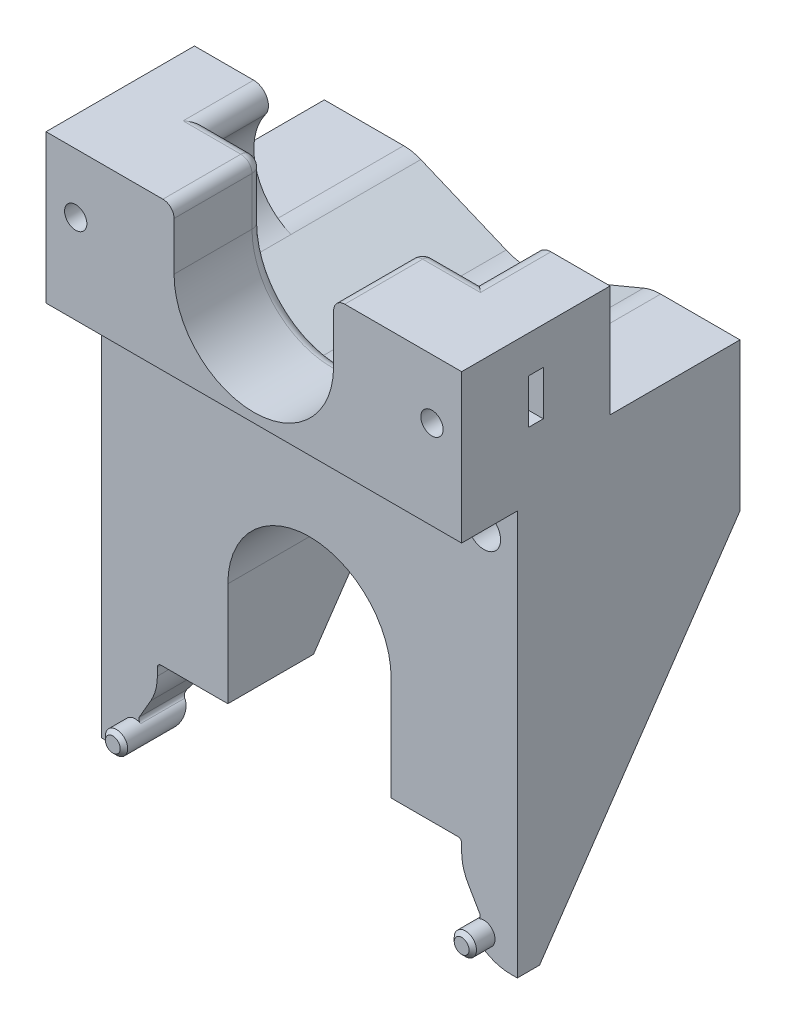
SolidWorks part; units mm, degrees
ref_plane "Front Plane" through (0, 0, 0) normal (0, 0, 1) x (1, 0, 0)
ref_plane "Top Plane" through (0, 0, 0) normal (0, 1, 0) x (1, 0, 0)
ref_plane "Right Plane" through (0, 0, 0) normal (1, 0, 0) x (0, 0, -1)
sketch "Sketch2" plane through (0, 0, 0) normal (0, 0, 1) x (1, 0, 0)
  line L0 (0, 28) -> (0, 0) construction
  line L1 (-23.5, -23.5) -> (23.5, -23.5) construction
  line L2 (-23.5, -23.5) -> (-23.5, 23.5) construction
  line L3 (-23.5, 23.5) -> (23.5, 23.5) construction
  line L4 (23.5, -23.5) -> (23.5, 23.5) construction
  line L5 (-23.5, -23.5) -> (23.5, 23.5) construction
  line L6 (-23.5, 23.5) -> (23.5, -23.5) construction
  line L7 (-28, -37) -> (28, -37) construction
  line L8 (-28, -37) -> (-28, 28) construction
  line L9 (-28, 28) -> (28, 28) construction
  line L10 (28, -37) -> (28, 28) construction
  line L11 (0, 0) -> (-28, 0) construction
  line L12 (-23.5, -25.5) -> (-23.5, -26.5) construction
  line L13 (-23.5, -26.5) -> (23.5, -26.5) construction
  line L14 (23.5, -26.5) -> (23.5, -25.5) construction
  line L15 (-23.5, -25.5) -> (23.5, -25.5) construction
  line L16 (0, 28) -> (0, 29.5) construction
  line L17 (0, 29.5) -> (0, 40) construction
  circle A0 centre (23.5, 23.5) radius 2 construction
  circle A1 centre (-23.5, 23.5) radius 2.25
  circle A2 centre (-23.5, -23.5) radius 1.5
  circle A3 centre (23.5, -23.5) radius 2 construction
  circle A4 centre (23.5, 23.5) radius 2.25
  circle A5 centre (23.5, -23.5) radius 1.5
  circle A6 centre (0, 40) radius 10.5 construction
  point P0 (0, 0)
  dimension "D3" = 4
  dimension "D8" = 21
  dimension "D1" = 47
  dimension "D5" = 56
  dimension "D6" = 65
  dimension "D7" = 1
  dimension "D9" = 1.5
  dimension "D4" = 0.5
sketch "Sketch3" plane through (0, 0, 0) normal (1, 0, 0) x (0, 0, -1)
  line L0 (0, -26.5) -> (0, 0)
  line L1 (0, 0) -> (0, 28)
  line L3 (30, 48) -> (30, 13)
  line L4 (30, 13) -> (3, -26.5)
  line L5 (3, -26.5) -> (0, -26.5)
  line L6 (30, 48) -> (-7.5, 48)
  line L7 (-7.5, 48) -> (-7.5, 28)
  line L8 (-7.5, 28) -> (0, 28)
  line L9 (0, 28) -> (30, 28) construction
  line L10 (3, -26.5) -> (22.1727, -26.5) construction
  dimension "D1" = 15
  dimension "D2" = 20
  dimension "D3" = 30
  dimension "D4" = 3
  dimension "D5" = 55.646
  dimension "D6" = 7.5
extrude "Boss-Extrude1" add sketch "Sketch3" along normal up to vertex (28 mm away) and the other way up to vertex (28 mm away) up to point (28, 28, 0) other way up to point (-28, 28, 0)
sketch "Sketch4" plane through (0, 0, 0) normal (0, 0, 1) x (1, 0, 0)
  line L0 (-28, -26.5) -> (-27.1213, -26.5) construction
  line L1 (-23.5, -26.5) -> (23.5, -26.5) construction
  line L2 (28, -26.5) -> (-28, -26.5) construction
  line L3 (-22.933, -21.5179) -> (-21.3871, -18.8403)
  line L4 (-27.1213, -26.5) -> (27.1213, -26.5)
  line L5 (0, 28) -> (0, -26.5) construction
  line L6 (-23.5, -23.5) -> (-23.5, 23.5) construction
  line L7 (-23.5, -23.5) -> (-22.75, -22.201) construction
  line L8 (-23.5, -23.5) -> (-22.4393, -24.5607) construction
  line L9 (-23.5, -23.5) -> (23.5, 23.5) construction
  line L10 (-22, -23.5) -> (-20.5, -23.5) construction
  line L11 (-23.5, -23.5) -> (23.5, -23.5) construction
  line L12 (-20.5, -15.5297) -> (-20.5, -14.5)
  line L13 (-20.5, -15.5297) -> (-20.5, -23.5) construction
  line L14 (-28, 28) -> (28, 28) construction
  line L15 (-20, -14) -> (-11, -14)
  line L16 (0, 0) -> (-28, 0) construction
  line L17 (-11, 0) -> (-11, -14)
  line L19 (28, -26.5) -> (27.1213, -26.5) construction
  line L20 (11, 0) -> (11, -14)
  line L21 (20, -14) -> (11, -14)
  line L22 (20.5, -15.5297) -> (20.5, -14.5)
  line L23 (22.933, -21.5179) -> (21.3871, -18.8403)
  arc A0 (-22.4393, -24.5607) -> (-22.75, -22.201) centre (-23.5, -23.5) ccw
  circle A1 centre (-23.5, -23.5) radius 1.5 construction
  arc A2 (-22.4393, -24.5607) -> (-27.1213, -26.5) centre (-27.1213, -19.8787) cw
  arc A3 (-22.75, -22.201) -> (-22.933, -21.5179) centre (-22.5, -21.7679) cw
  arc A4 (-21.3871, -18.8403) -> (-20.5, -15.5297) centre (-27.1213, -15.5297) ccw
  arc A5 (-11, 0) -> (11, 0) centre (0, 0) cw
  arc A6 (-20.5, -14.5) -> (-20, -14) centre (-20, -14.5) cw
  arc A7 (20.5, -14.5) -> (20, -14) centre (20, -14.5) ccw
  arc A8 (21.3871, -18.8403) -> (20.5, -15.5297) centre (27.1213, -15.5297) cw
  arc A9 (22.75, -22.201) -> (22.933, -21.5179) centre (22.5, -21.7679) ccw
  arc A10 (22.4393, -24.5607) -> (27.1213, -26.5) centre (27.1213, -19.8787) ccw
  arc A11 (22.4393, -24.5607) -> (22.75, -22.201) centre (23.5, -23.5) cw
  dimension "D1" = 0.5
  dimension "D5" = 22
  dimension "D2" = 30
  dimension "D3" = 1.5
  dimension "D4" = 42
extrude "Cut-Extrude1" cut sketch "Sketch4" against normal up to next
sketch "Sketch5" plane through (0, 0, 0) normal (0, 0, 1) x (1, 0, 0)
  circle A0 centre (23.5, -23.5) radius 1.5 construction
  circle A1 centre (-23.5, -23.5) radius 1.5 construction
  circle A2 centre (23.5, -23.5) radius 1.5
  circle A3 centre (-23.5, -23.5) radius 1.5
extrude "Boss-Extrude2" add sketch "Sketch5" along normal blind 3
chamfer "Chamfer1" distance 0.5 angle 45 2 edges at (25, -23.5, 3) (-22, -23.5, 3)
sketch "Sketch6" plane through (0, 0, 0) normal (0, 0, 1) x (1, 0, 0)
  circle A0 centre (23.5, 23.5) radius 2.25 construction
  circle A1 centre (-23.5, 23.5) radius 2.25 construction
  circle A2 centre (23.5, 23.5) radius 2.25
  circle A3 centre (-23.5, 23.5) radius 2.25
extrude "Cut-Extrude2" cut sketch "Sketch6" against normal up to next
sketch "Sketch7" plane through (0, 0, -30) normal (0, 0, -1) x (-1, 0, 0)
  circle A0 centre (-23.5, 23.5) radius 3.75
  circle A1 centre (23.5, 23.5) radius 3.5 construction
  circle A2 centre (23.5, 23.5) radius 3.75
  dimension "D2" = 7
  dimension "D1" = 0.25
extrude "Cut-Extrude3" cut sketch "Sketch7" against normal blind 3
sketch "Sketch8" plane through (0, 0, -30) normal (0, 0, -1) x (-1, 0, 0)
  line L4 (-10.5, 40) -> (10.5, 40) construction
  line L5 (-10.75, 40) -> (-10.75, 48)
  line L6 (-28, 48) -> (28, 48) construction
  line L7 (-10.75, 48) -> (10.75, 48)
  line L8 (10.75, 48) -> (10.75, 40)
  arc A0 (-10.5, 40) -> (10.5, 40) centre (0, 40) ccw construction
  circle A1 centre (0, 40) radius 10.5 construction
  arc A2 (-10.75, 40) -> (10.75, 40) centre (0, 40) ccw
  dimension "D1" = 0.25
extrude "Cut-Extrude4" cut sketch "Sketch8" against normal up to next
sketch "Sketch9" plane through (0, 0, -30) normal (0, 0, -1) x (-1, 0, 0)
  line L1 (3.5, 27.7009) -> (15.0026, 32.5)
  line L2 (0, 40) -> (20, 40) construction
  line L3 (0, 40) -> (0, 27) construction
  line L4 (10.75, 48) -> (28, 48) construction
  line L5 (20.0311, 48) -> (-20.0311, 48)
  line L6 (0, 48) -> (0, 40) construction
  line L7 (-3.5, 27.7009) -> (-15.0026, 32.5)
  arc A0 (-3.5, 27.7009) -> (3.5, 27.7009) centre (0, 36.0897) ccw
  arc A1 (18.42, 44.815) -> (15.0026, 32.5) centre (11.8734, 40) cw
  arc A2 (18.42, 44.815) -> (20.0311, 48) centre (20.0311, 46) cw
  arc A3 (-18.42, 44.815) -> (-15.0026, 32.5) centre (-11.8734, 40) ccw
  arc A4 (-18.42, 44.815) -> (-20.0311, 48) centre (-20.0311, 46) ccw
  dimension "D1" = 20
  dimension "D2" = 7.5
  dimension "D5" = 2
  dimension "D3" = 13
  dimension "D4" = 3.5
extrude "Cut-Extrude5" cut sketch "Sketch9" against normal offset from surface (25.5 mm away) 12 up to face at (0, 39.6563, 7.5)
fillet "Fillet1" radius 1.5 7 edges at (-10.75, 44, -4.5) (0, 29.25, -4.5) (-15.3905, 48, -4.5) (-10.75, 48, 1.5) (10.75, 44, -4.5) (10.75, 48, 1.5) (15.3905, 48, -4.5)
sketch "Sketch10" plane through (0, 0, -30) normal (0, 0, -1) x (-1, 0, 0)
  line L0 (3.5, 27.7009) -> (15.0026, 32.5) construction
  line L1 (17.3129, 32.9626) -> (28, 32.9626)
  line L2 (28, 13) -> (28, 48) construction
  line L3 (20.0311, 48) -> (28, 48) construction
  line L4 (20.0311, 48) -> (28, 48)
  line L5 (28, 32.9626) -> (28, 48)
  line L6 (0, 52.0975) -> (0, 21.7333) construction
  line L7 (-17.3129, 32.9626) -> (-28, 32.9626)
  line L8 (-20.0311, 48) -> (-28, 48)
  line L9 (-28, 32.9626) -> (-28, 48)
  arc A0 (17.3129, 32.9626) -> (15.0026, 32.5) centre (17.3129, 26.9626) ccw
  arc A1 (20.0311, 48) -> (18.42, 44.815) centre (20.0311, 46) ccw construction
  arc A2 (15.0026, 32.5) -> (18.42, 44.815) centre (11.8734, 40) ccw construction
  arc A3 (20.0311, 48) -> (18.42, 44.815) centre (20.0311, 46) ccw
  arc A4 (15.0026, 32.5) -> (18.42, 44.815) centre (11.8734, 40) ccw
  arc A5 (-17.3129, 32.9626) -> (-15.0026, 32.5) centre (-17.3129, 26.9626) cw
  arc A6 (-15.0026, 32.5) -> (-18.42, 44.815) centre (-11.8734, 40) cw
  arc A7 (-20.0311, 48) -> (-18.42, 44.815) centre (-20.0311, 46) cw
  dimension "D1" = 6
extrude "Cut-Extrude6" cut sketch "Sketch10" against normal offset from surface (17.5 mm away) 8 up to face at (0, 38.4455, -4.5)
sketch "Sketch11" plane through (0, 0, -12.5) normal (0, 0, -1) x (-1, 0, 0)
  line L0 (20, 40) -> (28, 40) construction
  line L1 (28, 48) -> (28, 32.9626) construction
  line L2 (20, 40) -> (0, 40) construction
  line L3 (0, 35.0058) -> (0, 45.4651) construction
  circle A0 centre (24, 40) radius 1.25 construction
  arc A2 (15.0026, 32.5) -> (18.42, 44.815) centre (11.8734, 40) ccw construction
  circle A3 centre (24, 40) radius 1.5
  circle A4 centre (-24, 40) radius 1.5
  point P10 (24, 40)
  dimension "D1" = 0.25
  dimension "D2" = 2.5
extrude "Cut-Extrude7" cut sketch "Sketch11" against normal up to next
ref_plane "Plane1" through (0, 0, -2.5) normal (0, 0, -1) x (-1, 0, 0)
sketch "Sketch12" plane through (0, 0, -2.5) normal (0, 0, -1) x (-1, 0, 0)
  line L0 (21, 37) -> (28, 37)
  line L1 (21.25, 37.25) -> (26.75, 37.25) construction
  line L2 (21.25, 37.25) -> (21.25, 42.75) construction
  line L3 (21.25, 42.75) -> (26.75, 42.75) construction
  line L4 (26.75, 37.25) -> (26.75, 42.75) construction
  line L5 (21.25, 37.25) -> (26.75, 42.75) construction
  line L6 (21.25, 42.75) -> (26.75, 37.25) construction
  line L7 (21, 37) -> (21, 43)
  line L8 (21, 43) -> (28, 43)
  line L9 (21, 37) -> (26.75, 37) construction
  line L10 (21, 43) -> (26.75, 43) construction
  line L11 (28, 13) -> (28, 32.9626) construction
  line L12 (28, 43) -> (28, 37)
  line L13 (0, 44.7133) -> (0, 38.4938) construction
  line L14 (-28, 43) -> (-28, 37)
  line L15 (-21, 37) -> (-28, 37)
  line L16 (-21, 37) -> (-21, 43)
  line L17 (-21, 43) -> (-28, 43)
  circle A0 centre (24, 40) radius 1.5 construction
  point P0 (24, 40)
  dimension "D1" = 5.5
extrude "Cut-Extrude8" cut sketch "Sketch12" against normal mid plane 2
equation "\"Tolerance\" = 0.25mm"
equation "\"Pocket_Head_M5\"= 8mm"
equation "\"Pocket_Head_M4\" = 7mm"
equation "\"Pocket_Nut_M4\" = 7mm"
equation "\"Pocket_Nut_M5\"= 8mm"
equation "\"Pocket_Nut_M3\"= 5.5mm"
equation "\"Pocket_Head_M3\"= 5.5mm"
equation "\"D2@Sketch2\"=\"Tolerance\""
equation "\"D4@Sketch2\" = ( \"Tolerance\" * 2 )"
equation "\"D1@Sketch7\"=\"Tolerance\""
equation "\"D2@Sketch7\"=\"Pocket_Head_M4\""
equation "\"D1@Sketch8\"=\"Tolerance\""
equation "\"D1@Sketch11\"=\"Tolerance\""
equation "\"D1@Sketch12\"=\"Pocket_Nut_M3\""
equation "\"D2@Sketch12\"=\"Tolerance\""
equation "\"D1@Cut-Extrude8\"=( 1.5 + ( \"Tolerance\" * 2 ) )"
